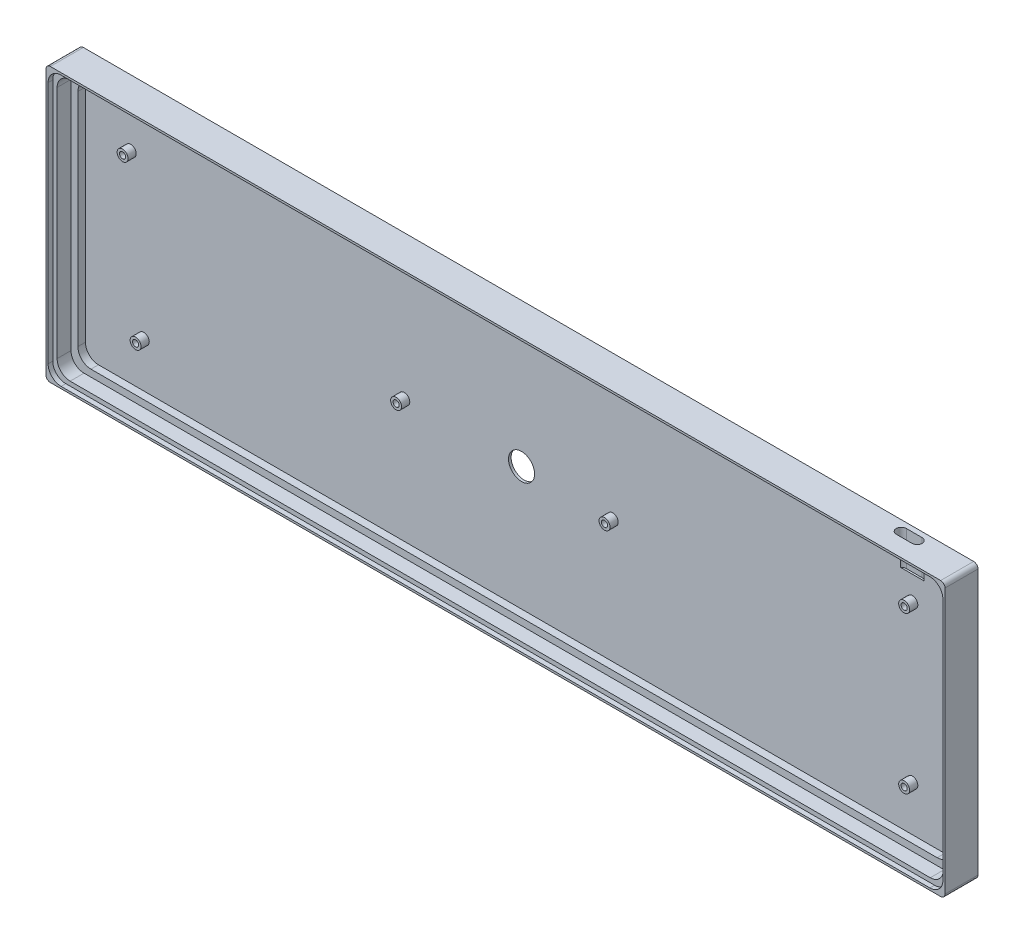
SolidWorks part; units mm, degrees
note: The reader was unsure of these and kept them because the rebuilt part matched: shared geometry of "Sketch1<3>", "Sketch1<4>", "Sketch1<5>".
ref_plane "Front" through (0, 0, 0) normal (0, 0, 1) x (1, 0, 0)
ref_plane "Top" through (0, 0, 0) normal (0, 1, 0) x (1, 0, 0)
ref_plane "Right" through (0, 0, 0) normal (1, 0, 0) x (0, 0, -1)
sketch "Sketch1" plane through (0, 0, 0) normal (0, 0, 1) x (1, 0, 0)
  line L0 (164.338, 50.038) -> (-164.338, 50.038)
  line L1 (161.9885, -47.6885) -> (-161.9885, -47.6885)
  line L2 (161.9885, -47.6885) -> (161.9885, 47.6885)
  line L3 (161.9885, 47.6885) -> (-161.9885, 47.6885)
  line L4 (-161.9885, -47.6885) -> (-161.9885, 47.6885)
  line L5 (0, 47.6885) -> (0, -47.6885) construction
  line L6 (161.9885, 0) -> (-161.9885, 0) construction
  line L7 (163.576, -49.276) -> (-163.576, -49.276)
  line L8 (163.576, -49.276) -> (163.576, 49.276)
  line L9 (163.576, 49.276) -> (-163.576, 49.276)
  line L10 (-163.576, -49.276) -> (-163.576, 49.276)
  line L11 (0, 49.276) -> (0, -49.276) construction
  line L12 (163.576, 0) -> (-163.576, 0) construction
  line L13 (-164.338, -50.038) -> (-164.338, 50.038)
  line L14 (164.338, -50.038) -> (-164.338, -50.038)
  line L15 (164.338, -50.038) -> (164.338, 50.038)
  line L16 (159.4485, 45.1485) -> (-159.4485, 45.1485)
  line L17 (-159.4485, -45.1485) -> (-159.4485, 45.1485)
  line L18 (159.4485, -45.1485) -> (-159.4485, -45.1485)
  line L19 (159.4485, -45.1485) -> (159.4485, 45.1485)
  point P0 (0, 0)
  point P4 (0, 0)
  dimension "D1" = 95.377
  dimension "D2" = 323.977
  dimension "D3" = 1.5875
  dimension "D4" = 1.5875
  dimension "D5" = 0.762
  dimension "D6" = 2.54
extrude "Boss-Extrude1" add sketch "Sketch1" along normal blind 2.54 contours L4 L1 L2 L3 | L10 L7 L8 L9 L1 L4 L3 L2 | L14 L15 L0 L13 L7 L10 L9 L8 | L18 L19 L16 L17
extrude "Boss-Extrude2" add sketch "Sketch1<3>" along normal blind 12.065 contours L14 L15 L0 L13 L7 L10 L9 L8
sketch "Sketch1<3>" plane through (0, 0, 0) normal (0, 0, 1) x (1, 0, 0) same geometry as "Sketch1"
extrude "Boss-Extrude3" add sketch "Sketch1<4>" along normal offset from surface (10.3505 mm away) 1.7145 contours L10 L7 L8 L9 L1 L4 L3 L2 up to face at (0, 0, 12.065)
sketch "Sketch1<4>" plane through (0, 0, 0) normal (0, 0, 1) x (1, 0, 0) same geometry as "Sketch1"
extrude "Boss-Extrude4" add sketch "Sketch1<5>" along normal offset from surface (5.2832 mm away) 5.0673 contours L4 L1 L2 L3 L19 L18 L17 L16 up to face at (0, 0, 10.3505)
sketch "Sketch1<5>" plane through (0, 0, 0) normal (0, 0, 1) x (1, 0, 0) same geometry as "Sketch1"
sketch "Sketch2" plane through (0, 0, 2.54) normal (0, 0, 1) x (1, 0, 0)
  circle A0 centre (-142.875, 28.575) radius 1.1306
  circle A1 centre (-138.1125, -28.575) radius 1.1306
  circle A2 centre (-42.8625, 0) radius 1.1306
  circle A3 centre (33.3375, 0) radius 1.1306
  circle A4 centre (142.875, -28.575) radius 2
  circle A5 centre (33.3375, 0) radius 2
  circle A6 centre (142.875, 28.575) radius 2
  circle A7 centre (-42.8625, 0) radius 2
  circle A12 centre (142.875, -28.575) radius 1.1306
  circle A13 centre (142.875, 28.575) radius 1.1306
  circle A14 centre (-138.1125, -28.575) radius 2
  circle A15 centre (-142.875, 28.575) radius 2
  dimension "D2" = 2.2611
  dimension "D1" = 4
extrude "Boss-Extrude5" add sketch "Sketch2" along normal offset from surface (2.9972 mm away) 0.254 contours A4 A12 | A6 A13 | A7 A2 | A5 A3 | A15 A0 | A14 A1 up to face at (0, 0, 5.2832) offset beyond the face yes
fillet "Fillet1" radius 4.7625 12 edges at (-163.576, -49.276, 11.2077) (-161.9885, -47.6885, 7.8168) (161.9885, -47.6885, 7.8168) (163.576, -49.276, 11.2077) (161.9885, 47.6885, 7.8168) (163.576, 49.276, 11.2077) (-161.9885, 47.6885, 7.8168) (-163.576, 49.276, 11.2077) (-159.4485, -45.1485, 3.9116) (159.4485, -45.1485, 3.9116) (159.4485, 45.1485, 3.9116) (-159.4485, 45.1485, 3.9116)
fillet "Fillet2" radius 1.5875 4 edges at (164.338, -50.038, 6.0325) (-164.338, -50.038, 6.0325) (-164.338, 50.038, 6.0325) (164.338, 50.038, 6.0325)
sketch "Sketch3" plane through (0, 0, 0) normal (0, 0, -1) x (-1, 0, 0)
  line L1 (-26.9875, -15.875) -> (26.9875, -15.875)
  line L2 (-30.1625, -12.7) -> (-30.1625, 12.7)
  line L3 (-26.9875, 15.875) -> (26.9875, 15.875)
  line L4 (30.1625, -12.7) -> (30.1625, 12.7)
  line L5 (0, 15.875) -> (0, -15.875) construction
  line L6 (-30.1625, 0) -> (30.1625, 0) construction
  arc A0 (-26.9875, -15.875) -> (-30.1625, -12.7) centre (-26.9875, -12.7) cw
  arc A1 (-26.9875, 15.875) -> (-30.1625, 12.7) centre (-26.9875, 12.7) ccw
  arc A2 (26.9875, 15.875) -> (30.1625, 12.7) centre (26.9875, 12.7) cw
  arc A3 (26.9875, -15.875) -> (30.1625, -12.7) centre (26.9875, -12.7) ccw
  point P0 (0, 0)
  point P6 (-30.1625, -15.875)
  point P11 (30.1625, 15.875)
  point P14 (30.1625, -15.875)
  dimension "D3" = 3.175
  dimension "D1" = 60.325
  dimension "D2" = 31.75
extrude "Cut-Extrude1" cut sketch "Sketch3" against normal blind 1.5875
sketch "Sketch4" plane through (0, 0, 2.54) normal (0, 0, 1) x (1, 0, 0)
  circle A0 centre (0, 0) radius 4.7625
  dimension "D1" = 9.525
extrude "Cut-Extrude2" cut sketch "Sketch4" against normal through all
sketch "Sketch5" plane through (0, 50.038, 0) normal (0, 1, 0) x (1, 0, 0)
  line L0 (145.765, -3.7032) -> (139.985, -3.7032) construction
  line L1 (145.765, -5.5372) -> (139.985, -5.5372)
  line L2 (145.765, -1.8692) -> (139.985, -1.8692)
  line L3 (147.599, -3.7032) -> (138.151, -3.7032) construction
  arc A0 (145.765, -5.5372) -> (145.765, -1.8692) centre (145.765, -3.7032) ccw
  arc A1 (139.985, -1.8692) -> (139.985, -5.5372) centre (139.985, -3.7032) ccw
  arc A3 (145.765, -5.2832) -> (145.765, -2.1232) centre (145.765, -3.7032) ccw construction
  arc A5 (139.985, -2.1232) -> (139.985, -5.2832) centre (139.985, -3.7032) ccw construction
  point P2 (142.875, -3.7032)
  dimension "D1" = 0.254
extrude "Cut-Extrude3" cut sketch "Sketch5" against normal blind 12.7
sketch "Sketch6" plane through (0, 0, 5.2832) normal (0, 0, 1) x (1, 0, 0)
  line L0 (142.875, 49.276) -> (142.875, 48.4822) construction
  line L6 (138.151, 45.1485) -> (147.599, 45.1485)
  line L7 (158.8135, 49.276) -> (-158.8135, 49.276) construction
  line L8 (138.151, 45.1485) -> (138.151, 46.8947)
  line L9 (139.7385, 48.4822) -> (146.0115, 48.4822)
  line L10 (147.599, 45.1485) -> (147.599, 46.8947)
  line L11 (138.151, 45.1485) -> (147.599, 48.4822) construction
  line L12 (138.151, 48.4822) -> (147.599, 45.1485) construction
  line L14 (142.875, 48.4822) -> (142.875, 47.6885) construction
  line L15 (157.226, 47.6885) -> (-157.226, 47.6885) construction
  line L16 (-154.686, 45.1485) -> (138.5671, 45.1485) construction
  line L19 (138.151, 50.038) -> (138.151, 45.1485) construction
  line L20 (147.599, 45.1485) -> (147.599, 50.038) construction
  arc A0 (147.599, 46.8947) -> (146.0115, 48.4822) centre (146.0115, 46.8947) ccw
  arc A1 (138.151, 46.8947) -> (139.7385, 48.4822) centre (139.7385, 46.8947) cw
  point P4 (142.875, 46.8154)
  dimension "D1" = 1.5875
extrude "Cut-Extrude4" cut sketch "Sketch6" against normal up to next and the other way through all
sketch "Sketch7" plane through (0, 0, 0) normal (0, 0, -1) x (-1, 0, 0)
  line L0 (-164.338, -48.4505) -> (-164.338, 48.4505) construction
  line L1 (157.988, -43.688) -> (-157.988, -43.688) construction
  line L2 (157.988, -43.688) -> (157.988, 43.688) construction
  line L3 (157.988, 43.688) -> (-157.988, 43.688) construction
  line L4 (-157.988, -43.688) -> (-157.988, 43.688) construction
  line L5 (0, 43.688) -> (0, -43.688) construction
  line L6 (157.988, 0) -> (-157.988, 0) construction
  line L7 (-162.7505, 50.038) -> (162.7505, 50.038) construction
  circle A1 centre (-157.988, 43.688) radius 4.826
  circle A2 centre (-157.988, -43.688) radius 4.826
  circle A3 centre (157.988, -43.688) radius 4.826
  circle A4 centre (157.988, 43.688) radius 4.826
  point P0 (0, 0)
  dimension "D1" = 9.652
  dimension "D2" = 6.35
  dimension "D3" = 6.35
extrude "Cut-Extrude5" cut sketch "Sketch7" against normal blind 1.27
